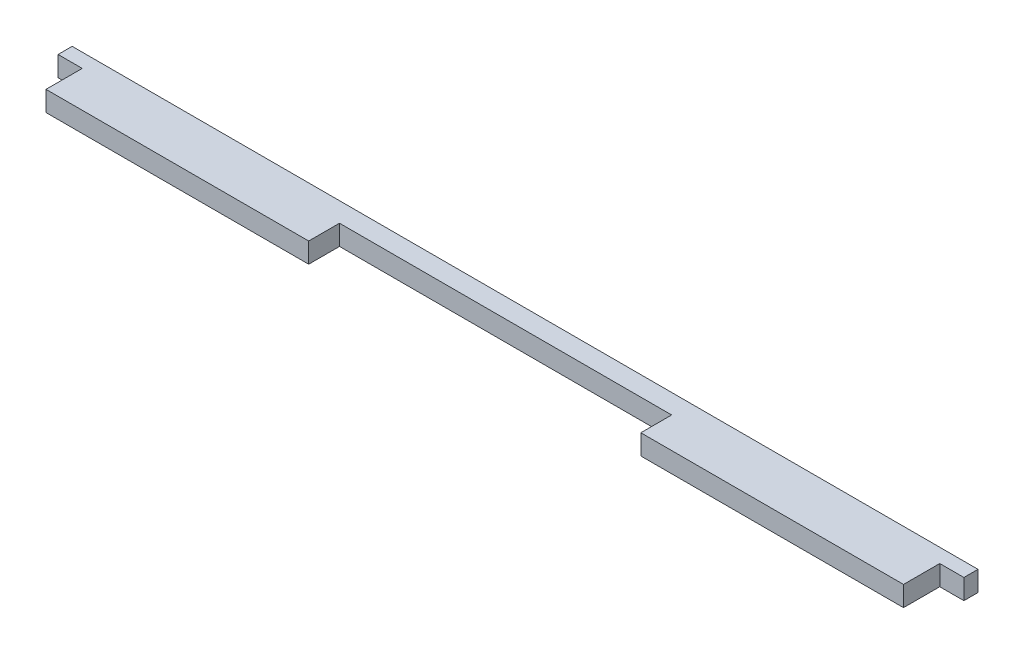
SolidWorks part; units mm, degrees
ref_plane "Front Plane" through (0, 0, 0) normal (0, 0, 1) x (1, 0, 0)
ref_plane "Top Plane" through (0, 0, 0) normal (0, 1, 0) x (1, 0, 0)
ref_plane "Right Plane" through (0, 0, 0) normal (1, 0, 0) x (0, 0, -1)
sketch "Sketch2" plane through (0, 0, 0) normal (0, 1, 0) x (1, 0, 0)
  line L1 (0, 0) -> (450, 0)
  line L2 (0, 0) -> (0, 25)
  line L3 (0, 25) -> (450, 25)
  line L4 (450, 0) -> (450, 25)
  line L5 (142.5, 0) -> (307.5, 0)
  line L6 (142.5, 0) -> (142.5, 15.3096)
  line L7 (142.5, 15.3096) -> (307.5, 15.3096)
  line L8 (307.5, 0) -> (307.5, 15.3096)
  point P9 (450, 12.5)
  dimension "D1" = 25
  dimension "D2" = 450
  dimension "D3" = 142.5
  dimension "D4" = 142.5
extrude "Boss-Extrude1" add sketch "Sketch2" along normal blind 10 contours L8 L1 L4 L3 L2 L6 L7 region at (4.5069, 0, -12.5)
sketch "Sketch3" plane through (0, 10, 0) normal (0, 1, 0) x (1, 0, 0)
  line L0 (225, 25) -> (225, 0) construction
  line L1 (0, 0) -> (12, 0)
  line L2 (0, 0) -> (0, 18)
  line L3 (0, 18) -> (12, 18)
  line L4 (12, 0) -> (12, 18)
  line L5 (0, 25) -> (450, 25) construction
  line L6 (450, 18) -> (438, 18)
  line L7 (438, 0) -> (438, 18)
  line L8 (450, 0) -> (438, 0)
  line L9 (450, 0) -> (450, 18)
  dimension "D1" = 18
  dimension "D2" = 12
extrude "Cut-Extrude1" cut sketch "Sketch3" against normal blind 10
